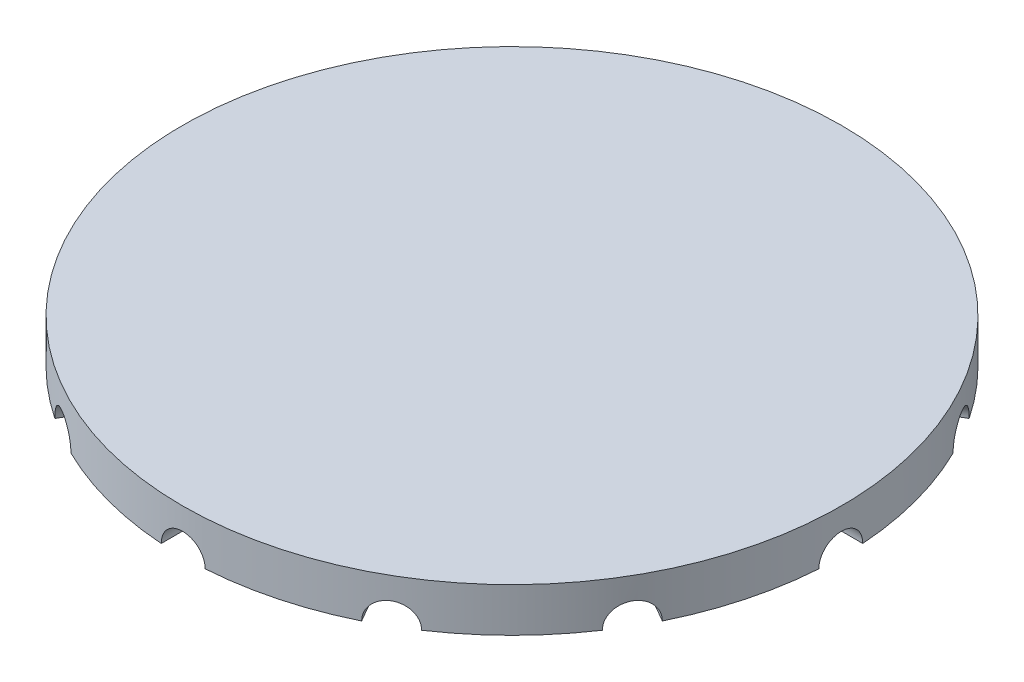
SolidWorks part; units mm, degrees
ref_plane "Спереди" through (0, 0, 0) normal (0, 0, 1) x (1, 0, 0)
ref_plane "Сверху" through (0, 0, 0) normal (0, 1, 0) x (1, 0, 0)
ref_plane "Справа" through (0, 0, 0) normal (1, 0, 0) x (0, 0, -1)
sketch "Эскиз1" plane through (0, 0, 0) normal (0, 1, 0) x (1, 0, 0)
  line L0 (0, -37.5) -> (0, 37.5) construction
  line L1 (-37.5, 0) -> (37.5, 0) construction
  line L2 (-2.5, 0) -> (-2.5, 60)
  line L3 (-2.5, 60) -> (0, 60)
  line L4 (0, 60) -> (0, 0)
  line L5 (0, 0) -> (-2.5, 0)
  circle A0 centre (0, 0) radius 37.5
  circle A1 centre (0, 0) radius 20
  point P6 (0, 0)
  point P9 (0, 0)
  dimension "D1" = 75
  dimension "D2" = 40
  dimension "D3" = 2.5
  dimension "D4" = 60
revolve "Повернуть2" add sketch "Эскиз1" angle 360 about L0 region at (-1.2484, 0, -9.974) region at (-1.2509, 0, -28.71) region at (-1.2508, 0, -48.7361)
extrude "Бобышка-Вытянуть1" add sketch "Эскиз1<5>" along normal blind 5 contours A1 L2 A0 L4 | A1 L4 A0 L2 region at (-13.9303, 0, 15.7955) region at (-1.2509, 0, -28.71)
sketch "Эскиз1<5>" plane through (0, 0, 0) normal (0, 1, 0) x (1, 0, 0) same geometry as "Эскиз1"
extrude "Бобышка-Вытянуть2" add sketch "Эскиз1<6>" along normal blind 5 contours L2 A1 L4 L5 | L4 A1 L2 L5 region at (0.0516, 0, 0.4122) region at (-1.2484, 0, -9.974)
sketch "Эскиз1<6>" plane through (0, 0, 0) normal (0, 1, 0) x (1, 0, 0) same geometry as "Эскиз1"
sketch "Эскиз2" plane through (0, 0, 0) normal (0, 0, 1) x (1, 0, 0)
  line L0 (0, 29.9571) -> (0, -29.9571) construction
  point P4 (0, 0)
sketch "Эскиз4" plane through (0, 0, -60) normal (0, 0, -1) x (-1, 0, 0)
  circle A0 centre (0, 0) radius 2.5 construction
  circle A1 centre (0, 0) radius 2.5
extrude "Вырез-Вытянуть1" cut sketch "Эскиз4" against normal up to vertex (60 mm away) up to point (0, -29.9571, 0)
pattern_circular "Круговой массив2" count 12 over 360 about axis through (0, 29.9571, 0) along (0, -1, 0) of "Вырез-Вытянуть1" reverse direction yes
sketch "Эскиз5" plane through (0, 0, 0) normal (0, -1, 0) x (1, 0, 0)
  circle A0 centre (0, 0) radius 20
  dimension "D1" = 40
extrude "Вырез-Вытянуть2" cut sketch "Эскиз5" against normal blind 2.5
sketch "Эскиз6" plane through (0, 0, 0) normal (0, -1, 0) x (1, 0, 0)
  line L0 (0, 37.5) -> (0, -37.5) construction
  line L1 (37.5, 0) -> (-37.5, 0) construction
  line L2 (2.5, -9.3301) -> (2.5, -60)
  line L3 (2.5, -60) -> (0, -60)
  line L4 (0, -60) -> (0, -9.3301)
  line L5 (0, -9.3301) -> (2.5, -9.3301)
  line L6 (0, 0) -> (10, -17.3205) construction
  line L7 (0, -50.7522) -> (2.5, -50.7522)
  line L8 (4.6651, -8.0801) -> (2.5, -9.3301) construction
  line L9 (2.5, -9.3301) -> (27.8349, -53.2115) construction
  line L10 (27.8349, -53.2115) -> (30, -51.9615) construction
  line L11 (30, -51.9615) -> (4.6651, -8.0801) construction
  arc A0 (-2.5, -37.4166) -> (2.5, -37.4166) centre (0, 0) ccw construction
  arc A1 (-37.4166, 2.5) -> (-37.4166, -2.5) centre (0, 0) ccw construction
  point P7 (0, 0)
  point P14 (0, 0)
  dimension "D1" = 2.5
  dimension "D2" = 60
  dimension "D3" = 60
  dimension "D4" = 2.5
